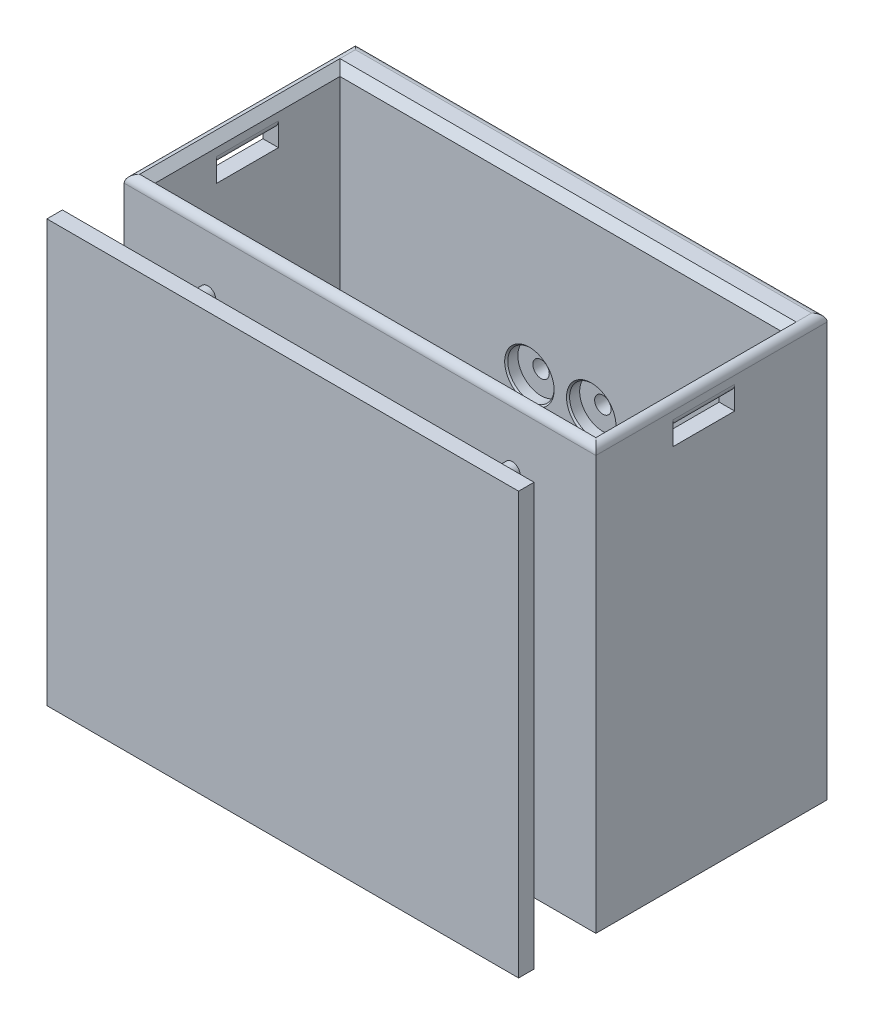
SolidWorks part; units mm, degrees
ref_plane "Front Plane" through (0, 0, 0) normal (0, 0, 1) x (1, 0, 0)
ref_plane "Top Plane" through (0, 0, 0) normal (0, 1, 0) x (1, 0, 0)
ref_plane "Right Plane" through (0, 0, 0) normal (1, 0, 0) x (0, 0, -1)
sketch "Sketch2" plane through (0, 0, 0) normal (0, 1, 0) x (1, 0, 0)
  line L1 (-90.551, -37.973) -> (90.551, -37.973)
  line L2 (-90.551, -37.973) -> (-90.551, 37.973)
  line L3 (-90.551, 37.973) -> (90.551, 37.973)
  line L4 (90.551, -37.973) -> (90.551, 37.973)
  line L5 (-90.551, -37.973) -> (90.551, 37.973) construction
  line L6 (-90.551, 37.973) -> (90.551, -37.973) construction
  line L7 (96.901, -44.323) -> (96.901, 50.673)
  line L8 (-96.901, -44.323) -> (96.901, -44.323)
  line L9 (-96.901, -44.323) -> (-96.901, 50.673)
  line L10 (-96.901, 44.323) -> (96.901, 44.323) construction
  line L11 (-96.901, 50.673) -> (96.901, 50.673)
  line L12 (-96.901, -44.323) -> (-96.901, 44.323) construction
  line L13 (96.901, -44.323) -> (96.901, 44.323) construction
  point P0 (0, 0)
  dimension "D1" = 6.35
  dimension "D2" = 181.102
  dimension "D3" = 75.946
  dimension "D4" = 12.7
extrude "Boss-Extrude1" add sketch "Sketch2" along normal blind 6.35 contours L1 L4 L3 L2 | L9 L8 L7 L4 L1 L2 L3 region at (0, 0, 0) region at (0, 0, 42.1647)
extrude "Boss-Extrude2" add sketch "Sketch2<3>" along normal blind 166.878 from surface starting at face at (0, 6.35, -3.175)
sketch "Sketch2<3>" plane through (0, 0, 0) normal (0, 1, 0) x (1, 0, 0) same geometry as "Sketch2"
sketch "Sketch3" plane through (0, 0, -37.973) normal (0, 0, 1) x (1, 0, 0)
  line L1 (-12.7, 77.089) -> (12.7, 77.089) construction
  line L2 (-12.7, 77.089) -> (-12.7, 102.489) construction
  line L3 (-12.7, 102.489) -> (12.7, 102.489) construction
  line L4 (-90.551, 6.35) -> (90.551, 6.35)
  line L5 (90.551, 6.35) -> (90.551, 173.228)
  line L6 (90.551, 173.228) -> (-90.551, 173.228)
  line L7 (-90.551, 173.228) -> (-90.551, 6.35)
  line L8 (-90.551, 6.35) -> (90.551, 6.35)
  line L9 (90.551, 6.35) -> (90.551, 173.228)
  line L10 (90.551, 173.228) -> (-90.551, 173.228)
  line L11 (-90.551, 173.228) -> (-90.551, 6.35)
  line L12 (12.7, 77.089) -> (12.7, 102.489) construction
  line L13 (-12.7, 77.089) -> (12.7, 102.489) construction
  line L14 (-12.7, 102.489) -> (12.7, 77.089) construction
  circle A0 centre (-12.7, 102.489) radius 3.175
  circle A1 centre (12.7, 102.489) radius 3.175
  circle A2 centre (12.7, 77.089) radius 3.175
  circle A3 centre (-12.7, 77.089) radius 3.175
  point P2 (0, 89.789)
  point P4 (12.7, 102.489)
  point P6 (-12.7, 77.089)
  point P7 (-12.7, 102.489)
  point P8 (12.7, 77.089)
  point P9 (-90.551, 89.789)
  point P12 (0, 6.35)
  point P23 (-90.551, 89.789)
  dimension "D3" = 6.35
  dimension "D2" = 25.4
  dimension "D1" = 0
sketch "Sketch9" plane through (0, 0, -37.973) normal (0, 0, 1) x (1, 0, 0)
  point P0 (-12.7, 102.489)
  point P2 (12.7, 102.489)
  point P5 (12.7, 77.089)
  point P8 (-12.7, 77.089)
hole_wizard "CBORE for 1/4 Hex Head Bolt2" positions "Sketch9" profile "Sketch8" counterbore size "1/4" standard "ANSI Inch" end condition through all
sketch "Sketch8" plane through (-12.7, 102.489, -37.973) normal (1, 0, 0) x (0, -1, 0)
  line L0 (0, 0) -> (0, 12.7)
  line L1 (0, 12.7) -> (3.3782, 12.7)
  line L3 (3.3782, 12.7) -> (3.3782, 4.7752)
  line L4 (9.525, 4.7752) -> (3.3782, 4.7752)
  line L5 (9.525, 4.7752) -> (9.525, 0.635)
  line L6 (9.525, 0.635) -> (10.16, 0)
  line L7 (10.16, 0) -> (0, 0)
  line L8 (-9.525, 0.635) -> (-10.16, 0) construction
  line L11 (0, -6.35) -> (0, 107.95) construction
  dimension "Thru Hole Dia." = 6.7564
  dimension "Thru Hole Depth" = 12.7
  dimension "C'Bore Dia." = 19.05
  dimension "C'Bore Depth" = 4.7752
  dimension "Near C'Sink Dia." = 20.32
  dimension "Near C'Sink Angle" = 90
sketch "Sketch10" plane through (0, 0, 44.323) normal (0, 0, 1) x (1, 0, 0)
  line L0 (-90.551, 173.228) -> (90.551, 6.35) construction
  line L1 (90.551, 173.228) -> (-90.551, 6.35) construction
  line L2 (90.551, 6.35) -> (62.5324, 32.168) construction
  line L3 (90.551, 173.228) -> (62.5324, 147.41) construction
  line L4 (-90.551, 6.35) -> (90.551, 6.35)
  line L5 (-90.551, 173.228) -> (-90.551, 6.35)
  line L6 (90.551, 173.228) -> (-90.551, 173.228)
  line L7 (90.551, 6.35) -> (90.551, 173.228)
  line L8 (-90.551, 6.35) -> (90.551, 6.35)
  line L9 (-90.551, 173.228) -> (-90.551, 6.35)
  line L10 (90.551, 173.228) -> (-90.551, 173.228)
  line L11 (90.551, 6.35) -> (90.551, 173.228)
  line L12 (-96.901, 0) -> (96.901, 0)
  line L13 (96.901, 0) -> (96.901, 173.228)
  line L14 (96.901, 173.228) -> (-96.901, 173.228)
  line L15 (-96.901, 173.228) -> (-96.901, 0)
  line L16 (-96.901, 0) -> (96.901, 0)
  line L17 (96.901, 0) -> (96.901, 173.228)
  line L18 (96.901, 173.228) -> (-96.901, 173.228)
  line L19 (-96.901, 173.228) -> (-96.901, 0)
  line L20 (-90.551, 173.228) -> (-62.5324, 147.41) construction
  line L21 (-90.551, 6.35) -> (-62.5324, 32.168) construction
  circle A0 centre (-62.5324, 147.41) radius 4.7625
  circle A1 centre (62.5324, 147.41) radius 4.7625
  circle A2 centre (62.5324, 32.168) radius 4.7625
  circle A3 centre (-62.5324, 32.168) radius 4.7625
  point P6 (62.5324, 147.41)
  point P8 (62.5324, 32.168)
  point P10 (-62.5324, 147.41)
  point P12 (-62.5324, 32.168)
  dimension "D3" = 9.525
  dimension "D4" = 38.1
sketch "Sketch12" plane through (0, 0, 44.323) normal (0, 0, 1) x (1, 0, 0)
  circle A0 centre (-62.5324, 32.168) radius 4.7625 construction
  circle A1 centre (62.5324, 32.168) radius 4.7625 construction
  circle A2 centre (62.5324, 147.41) radius 4.7625 construction
  circle A3 centre (-62.5324, 147.41) radius 4.7625 construction
  circle A4 centre (-62.5324, 32.168) radius 4.7625
  circle A5 centre (62.5324, 32.168) radius 4.7625
  circle A6 centre (62.5324, 147.41) radius 4.7625
  circle A7 centre (-62.5324, 147.41) radius 4.7625
  circle A8 centre (-62.5324, 147.41) radius 3.302
  circle A9 centre (62.5324, 147.41) radius 3.302
  circle A10 centre (62.5324, 32.168) radius 3.302
  circle A11 centre (-62.5324, 32.168) radius 3.302
  dimension "D1" = 6.604
extrude "Boss-Extrude3" add sketch "Sketch12" along normal blind 25.4 separate body contours A8 | A9 | A10 | A11 region at (-62.5324, 147.41, 44.323) region at (62.5324, 147.41, 44.323) region at (62.5324, 32.168, 44.323) region at (-62.5324, 32.168, 44.323)
sketch "Sketch13" plane through (0, 0, 44.323) normal (0, 0, 1) x (1, 0, 0)
  line L4 (-96.901, 0) -> (96.901, 0)
  line L5 (96.901, 0) -> (96.901, 173.228)
  line L6 (96.901, 173.228) -> (-96.901, 173.228)
  line L7 (-96.901, 173.228) -> (-96.901, 0)
  line L8 (-96.901, 0) -> (96.901, 0)
  line L9 (96.901, 0) -> (96.901, 173.228)
  line L10 (96.901, 173.228) -> (-96.901, 173.228)
  line L11 (-96.901, 173.228) -> (-96.901, 0)
  dimension "D1" = 0
extrude "Boss-Extrude4" add sketch "Sketch13" along normal blind 6.35 from surface separate body starting at face at (-59.2304, 147.41, 69.723)
sketch "Sketch16" plane through (96.901, 0, 0) normal (1, 0, 0) x (0, 0, -1)
  line L0 (0, 160.528) -> (0, 173.228) construction
  line L1 (-12.7, 157.353) -> (12.7, 157.353)
  line L2 (-12.7, 157.353) -> (-12.7, 163.703)
  line L3 (-12.7, 163.703) -> (12.7, 163.703)
  line L4 (-37.973, 6.35) -> (37.973, 6.35)
  line L5 (-37.973, 173.228) -> (-37.973, 6.35)
  line L6 (37.973, 173.228) -> (-37.973, 173.228)
  line L7 (37.973, 6.35) -> (37.973, 173.228)
  line L8 (-37.973, 6.35) -> (37.973, 6.35)
  line L9 (-37.973, 173.228) -> (-37.973, 6.35)
  line L10 (37.973, 173.228) -> (-37.973, 173.228)
  line L11 (37.973, 6.35) -> (37.973, 173.228)
  line L12 (12.7, 157.353) -> (12.7, 163.703)
  line L13 (-12.7, 157.353) -> (12.7, 163.703) construction
  line L14 (-12.7, 163.703) -> (12.7, 157.353) construction
  point P2 (0, 160.528)
  point P10 (0, 173.228)
  dimension "D2" = 12.7
  dimension "D3" = 25.4
  dimension "D4" = 6.35
  dimension "D1" = 0
extrude "Cut-Extrude2" cut sketch "Sketch16" against normal through all contours L1 L12 L3 L2 region at (96.901, 160.528, 0)
fillet "Fillet1" radius 3.175 4 edges at (90.551, 163.703, 0) (96.901, 163.703, 0) (-90.551, 163.703, 0) (-96.901, 163.703, 0)
fillet "Fillet2" radius 3.175 4 edges at (-96.901, 173.228, -3.175) (0, 173.228, 44.323) (96.901, 173.228, -3.175) (0, 173.228, -50.673)
chamfer "Chamfer1" distance 3.175 4 edges at (90.551, 173.228, 0) (0, 173.228, 37.973) (-90.551, 173.228, 0) (0, 173.228, -37.973)
equation "\"wall_thick\"= 0.25in"
equation "\"D1@Boss-Extrude1\"=\"wall_thick\""
equation "\"D1@Sketch2\"=\"wall_thick\""
equation "\"bolt_dia\"= 0.25in"
equation "\"D3@Sketch10\"=\"bolt_dia\"+0.125in"
